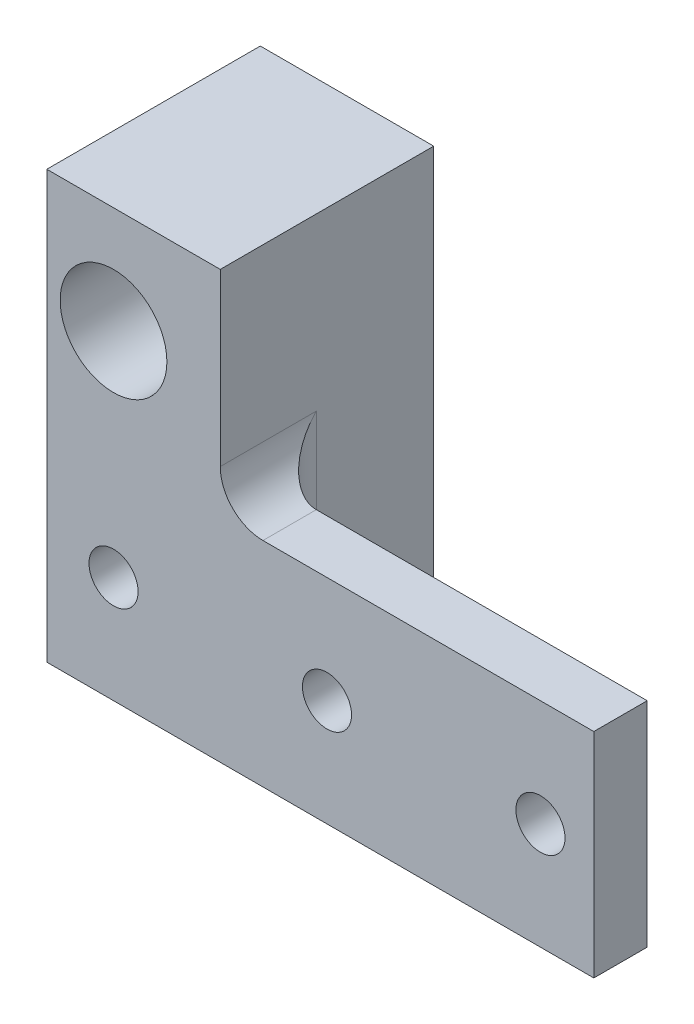
SolidWorks part; units mm, degrees
ref_plane "Front Plane" through (0, 0, 0) normal (0, 0, 1) x (1, 0, 0)
ref_plane "Top Plane" through (0, 0, 0) normal (0, 1, 0) x (1, 0, 0)
ref_plane "Right Plane" through (0, 0, 0) normal (1, 0, 0) x (0, 0, -1)
sketch "Sketch1" plane through (0, 0, 0) normal (0, 0, 1) x (1, 0, 0)
  line L0 (0, 0) -> (0, 50.8)
  line L1 (0, 50.8) -> (25.4, 50.8)
  line L2 (25.4, 50.8) -> (25.4, 25.4)
  line L3 (25.4, 25.4) -> (69.85, 25.4)
  line L4 (69.85, 25.4) -> (69.85, 0)
  line L5 (69.85, 0) -> (0, 0)
  dimension "D1" = 50.8
  dimension "D2" = 25.4
  dimension "2.75" = 69.85
extrude "Boss-Extrude1" add sketch "Sketch1" along normal blind 25.4
sketch "Sketch2" plane through (0, 0, 25.4) normal (0, 0, 1) x (1, 0, 0)
  line L0 (25.4, 50.8) -> (0, 50.8) construction
  line L1 (25.4, 25.4) -> (25.4, 50.8) construction
  line L2 (0, 0) -> (69.85, 0) construction
  circle A0 centre (12.7, 38.1) radius 2.921
  circle A1 centre (12.7, 12.7) radius 2.921
  circle A2 centre (38.1, 12.7) radius 2.921
  circle A3 centre (63.5, 12.7) radius 2.921
  dimension "D1" = 5.842
  dimension "D2" = 12.7
  dimension "D3" = 12.7
  dimension "D4" = 12.7
  dimension "D5" = 3
extrude "Cut-Extrude1" cut sketch "Sketch2" against normal through all
sketch "Sketch3" plane through (0, 0, 25.4) normal (0, 0, 1) x (1, 0, 0)
  line L0 (25.4, 50.8) -> (0, 50.8) construction
  line L1 (0, 0) -> (4.7625, 0)
  line L2 (0, 0) -> (0, 50.8)
  line L3 (0, 50.8) -> (4.7625, 50.8)
  line L4 (4.7625, 0) -> (4.7625, 50.8)
  dimension "D1" = 4.7625
extrude "Cut-Extrude2" cut sketch "Sketch3" against normal through all
sketch "Sketch4" plane through (0, 0, 0) normal (0, -1, 0) x (1, 0, 0)
  line L1 (69.85, 0) -> (25.4, 0)
  line L2 (69.85, 0) -> (69.85, 19.05)
  line L3 (69.85, 19.05) -> (25.4, 19.05)
  line L4 (25.4, 0) -> (25.4, 19.05)
  dimension "D1" = 19.05
  dimension "D2" = 44.45
extrude "Cut-Extrude3" cut sketch "Sketch4" against normal through all
fillet "Fillet1" radius 5.08 2 edges at (25.4, 12.7, 19.05) (25.4, 25.4, 22.225)
sketch "Sketch6" plane through (0, 0, 25.4) normal (0, 0, 1) x (1, 0, 0)
  circle A0 centre (12.7, 38.1) radius 6.35
  dimension "D1" = 12.7
extrude "Cut-Extrude5" cut sketch "Sketch6" against normal blind 12.7
